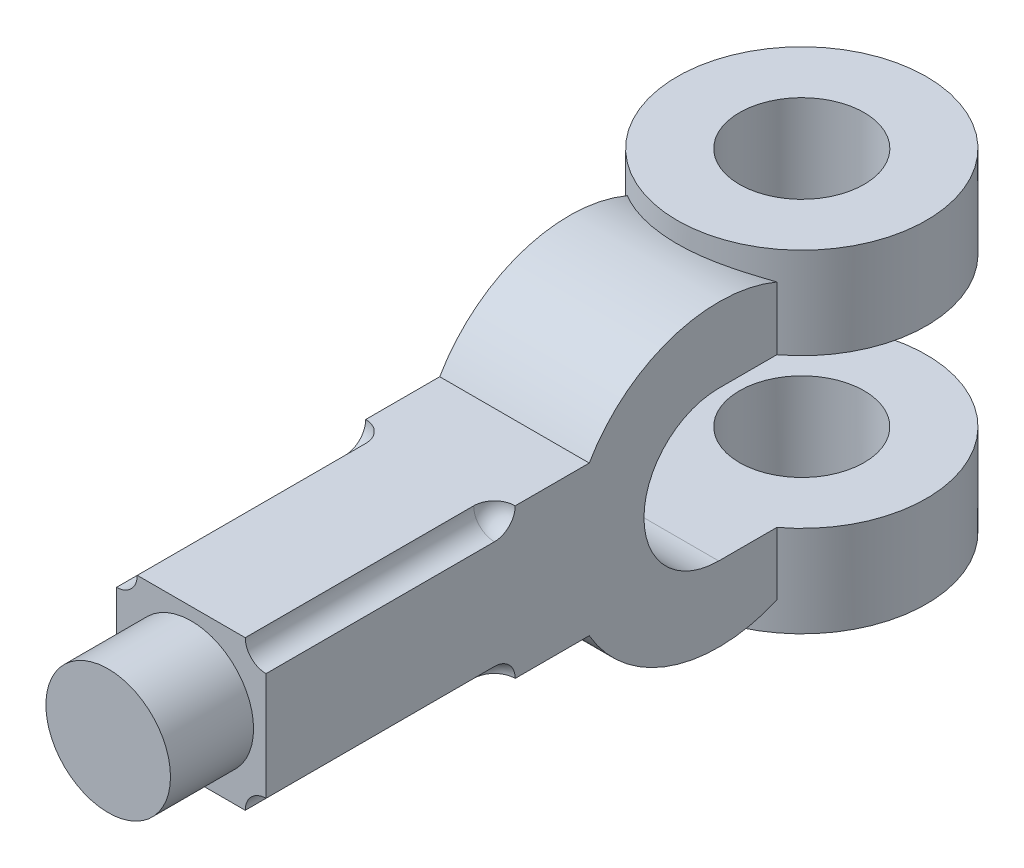
SolidWorks part; units mm, degrees
ref_plane "Front Plane" through (0, 0, 0) normal (0, 0, 1) x (1, 0, 0)
ref_plane "Top Plane" through (0, 0, 0) normal (0, 1, 0) x (1, 0, 0)
ref_plane "Right Plane" through (0, 0, 0) normal (1, 0, 0) x (0, 0, -1)
sketch "Sketch1" plane through (0, 0, 0) normal (1, 0, 0) x (0, 0, -1)
  circle A0 centre (0, 0) radius 36
  dimension "D1" = 72
extrude "Boss-Extrude1" add sketch "Sketch1" along normal mid plane 36
sketch "Sketch2" plane through (0, 0, 0) normal (0, 0, 1) x (1, 0, 0)
  line L0 (18, -36) -> (18, 36) construction
  line L1 (-18, 18) -> (18, 18)
  line L2 (-18, 18) -> (-18, -18)
  line L3 (-18, -18) -> (18, -18)
  line L4 (18, 18) -> (18, -18)
  line L5 (-18, 18) -> (18, -18) construction
  line L6 (-18, -18) -> (18, 18) construction
  point P0 (0, 0)
  dimension "D1" = 36
extrude "Boss-Extrude2" add sketch "Sketch2" along normal blind 109
sketch "Sketch3" plane through (0, 0, 109) normal (0, 0, 1) x (1, 0, 0)
  circle A0 centre (0, 0) radius 15
  dimension "D1" = 30
extrude "Boss-Extrude3" add sketch "Sketch3" along normal blind 20
sketch "Sketch4" plane through (0, 0, 0) normal (0, 1, 0) x (1, 0, 0)
  line L0 (18, -109) -> (-18, -109) construction
  circle A0 centre (0, 38) radius 30
  dimension "D2" = 60
  dimension "D1" = 147
extrude "Boss-Extrude4" add sketch "Sketch4" along normal mid plane 80
sketch "Sketch5" plane through (0, 0, 0) normal (1, 0, 0) x (0, 0, -1)
  line L0 (0, 18) -> (68, 18)
  line L1 (68, -40) -> (68, 40) construction
  line L2 (68, 18) -> (68, -18)
  line L3 (68, -18) -> (0, -18)
  arc A0 (0, 18) -> (0, -18) centre (0, 0) ccw
  dimension "D1" = 18
extrude "Cut-Extrude1" cut sketch "Sketch5" against normal through all both and the other way through all
hole_wizard "Hole1" positions "Sketch6" profile "Sketch7" legacy end condition through all
sketch "Sketch6" plane through (0, 40, 0) normal (0, 1, 0) x (1, 0, 0)
  point P0 (0, 38)
sketch "Sketch7" plane through (0, 40, -38) normal (1, 0, 0) x (0, 0, 1)
  line L0 (0, 0) -> (0, 80)
  line L1 (0, 80) -> (15, 80)
  line L2 (15, 80) -> (15, 0)
  line L3 (15, 0) -> (0, 0)
  line L4 (0, 110) -> (0, -10) construction
  dimension "Diameter" = 30
  dimension "Depth" = 80
sketch "Sketch8" plane through (0, 0, 109) normal (0, 0, 1) x (1, 0, 0)
  line L0 (18, 18) -> (-18, 18) construction
  line L1 (18, -18) -> (18, 18) construction
  line L2 (13, 18) -> (18, 18)
  line L3 (18, 18) -> (18, 13)
  arc A0 (13, 18) -> (18, 13) centre (18, 18) ccw
  dimension "D1" = 5
extrude "Cut-Extrude2" cut sketch "Sketch8" against normal blind 60 and the other way through all
fillet "Fillet1" radius 5 1 edges at (14.4645, 14.4645, 49)
pattern_circular "CirPattern1" count 4 over 360 about axis through (0, 0, 129) along (0, 0, 1) of "Cut-Extrude2", "Fillet1"
